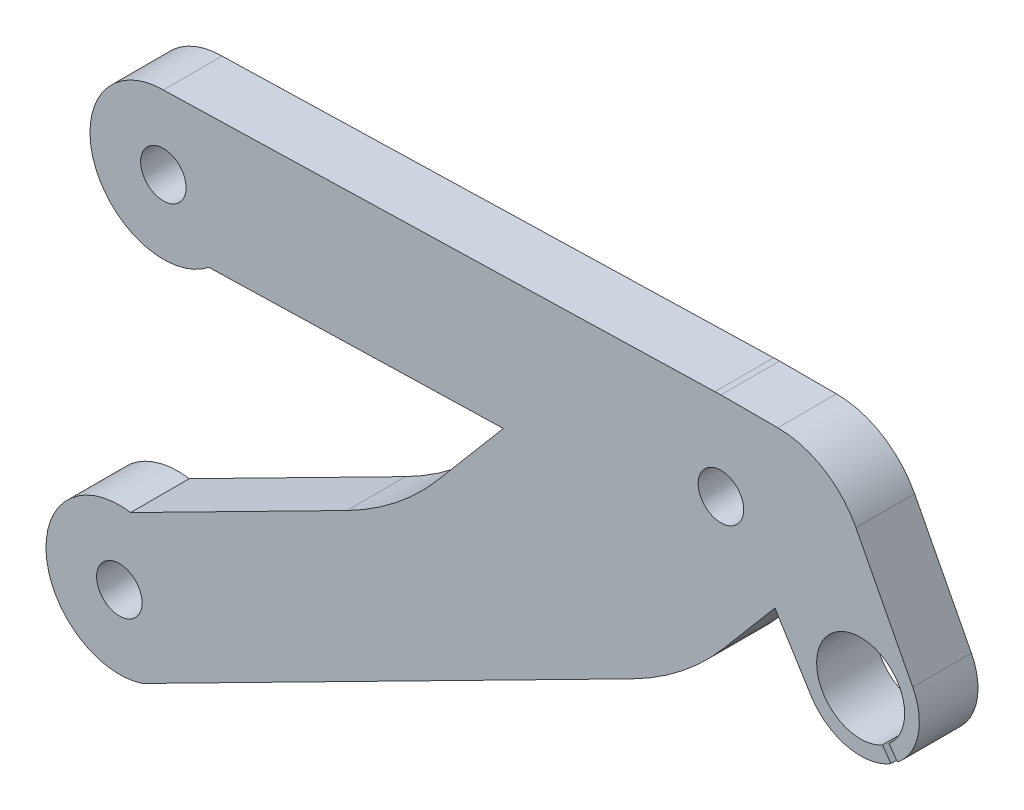
SolidWorks part; units mm, degrees
ref_plane "Front Plane" through (0, 0, 0) normal (0, 0, 1) x (1, 0, 0)
ref_plane "Top Plane" through (0, 0, 0) normal (0, 1, 0) x (1, 0, 0)
ref_plane "Right Plane" through (0, 0, 0) normal (1, 0, 0) x (0, 0, -1)
sketch "Sketch2" plane through (0, 0, 0) normal (0, 0, 1) x (1, 0, 0)
  line L0 (0, 0) -> (0, 26) construction
  line L1 (41, 26) -> (0, 26) construction
  line L2 (0, 0) -> (0, 26) construction
  line L3 (0, 26) -> (3, 26) construction
  line L4 (1.5758, -4.7452) -> (38.5983, 14.0699)
  line L5 (38.5983, 14.0699) -> (44.6837, 21.264)
  line L6 (3, 31) -> (40.5909, 31.986)
  line L10 (26.171, 22.6047) -> (19.1158, 14.2643)
  line L11 (19.1158, 14.2643) -> (0.7692, 4.9405)
  line L12 (6.1016, 22.0783) -> (26.171, 22.6047)
  circle A0 centre (0, 0) radius 1.55
  circle A1 centre (41, 26) radius 1.55
  circle A2 centre (3, 26) radius 1.55
  arc A3 (0.7692, 4.9405) -> (1.5758, -4.7452) centre (0, 0) ccw
  arc A4 (44.6837, 21.264) -> (40.5909, 31.986) centre (41, 26) ccw
  arc A5 (3, 31) -> (6.1016, 22.0783) centre (3, 26) ccw
  dimension "D1" = 3.1
  dimension "D2" = 3.1
  dimension "D3" = 3.1
  dimension "D8" = 10
  dimension "D9" = 12
  dimension "D10" = 10
  dimension "D5" = 41
  dimension "D6" = 26
  dimension "D7" = 3
  dimension "D11" = 9
  dimension "D12" = 9
  dimension "D13" = 15
extrude "Boss-Extrude1" add sketch "Sketch2" along normal blind 2 and the other way blind 2 contours L6 A5 A3 L4 L5 A4 A0 A1 A2 region at (-4.3468, -0.3619, 0)
fillet "Fillet1" radius 20 2 edges at (38.5983, 14.0699, 0) (19.1158, 14.2643, 0)
sketch "Sketch3" plane through (0, 0, 2) normal (0, 0, 1) x (1, 0, 0)
  line L0 (44.6837, 21.264) -> (26.4129, -0.3351)
  line L1 (41.2064, 17.1532) -> (44.6837, 21.264) construction
  line L2 (26.4129, -0.3351) -> (34.7488, -7.3866)
  line L3 (34.7488, -7.3866) -> (43.0769, 2.4586)
  line L4 (44.6837, 21.264) -> (53.0197, 14.2125)
  line L5 (53.0197, 14.2125) -> (44.6915, 4.3673)
  line L6 (43.0769, 2.4586) -> (30.2338, -2.2575)
  line L7 (30.2338, -2.2575) -> (47.213, 17.8147)
  line L8 (47.213, 17.8147) -> (44.6915, 4.3673)
  line L9 (30.2338, -2.2575) -> (29.588, -3.021) construction
  line L10 (47.213, 17.8147) -> (47.8588, 18.5781) construction
  dimension "D1" = 1
  dimension "D2" = 2.5
extrude "Boss-Extrude2" [suppressed] add sketch "Sketch3" against normal up to surface (10 mm away)
fillet "Fillet2" [suppressed] radius 1
sketch "Sketch4" plane through (0, 0, 2) normal (0, 0, 1) x (1, 0, 0)
  line L7 (41.2064, 17.1532) -> (44.6837, 21.264) construction
  line L8 (0, 0) -> (50000, 0) construction
  line L17 (44.6837, 21.264) -> (47.1283, 17.3372)
  line L18 (41.0014, 32) -> (48.527, 32)
  line L19 (48.527, 32) -> (54.0756, 21.2914)
  line L20 (52.0144, 16.8475) -> (52.5897, 16.0258)
  line L21 (52.461, 17.1603) -> (53.0363, 16.3386)
  line L22 (50.5241, 19.4512) -> (-28628.2978, 40977.0534) construction
  arc A0 (41.0014, 32) -> (44.6837, 21.264) centre (41, 26) cw
  arc A1 (44.6837, 21.264) -> (40.5909, 31.986) centre (41, 26) ccw construction
  arc A3 (52.461, 17.1603) -> (52.0144, 16.8475) centre (50.5241, 19.4512) ccw
  arc A4 (47.1283, 17.3372) -> (52.5897, 16.0258) centre (50.5241, 19.4512) ccw
  arc A5 (53.0363, 16.3386) -> (54.0756, 21.2914) centre (50.5241, 19.4512) ccw
  point P17 (0, 0)
  dimension "D1" = 6
  dimension "D2" = 8
  dimension "D3" = 55
extrude "Boss-Extrude3" add sketch "Sketch4" against normal up to surface (4 mm away) up to face at (1.55, 0, -2)
fillet "Fillet3" radius 6 1 edges at (48.527, 32, 0)
